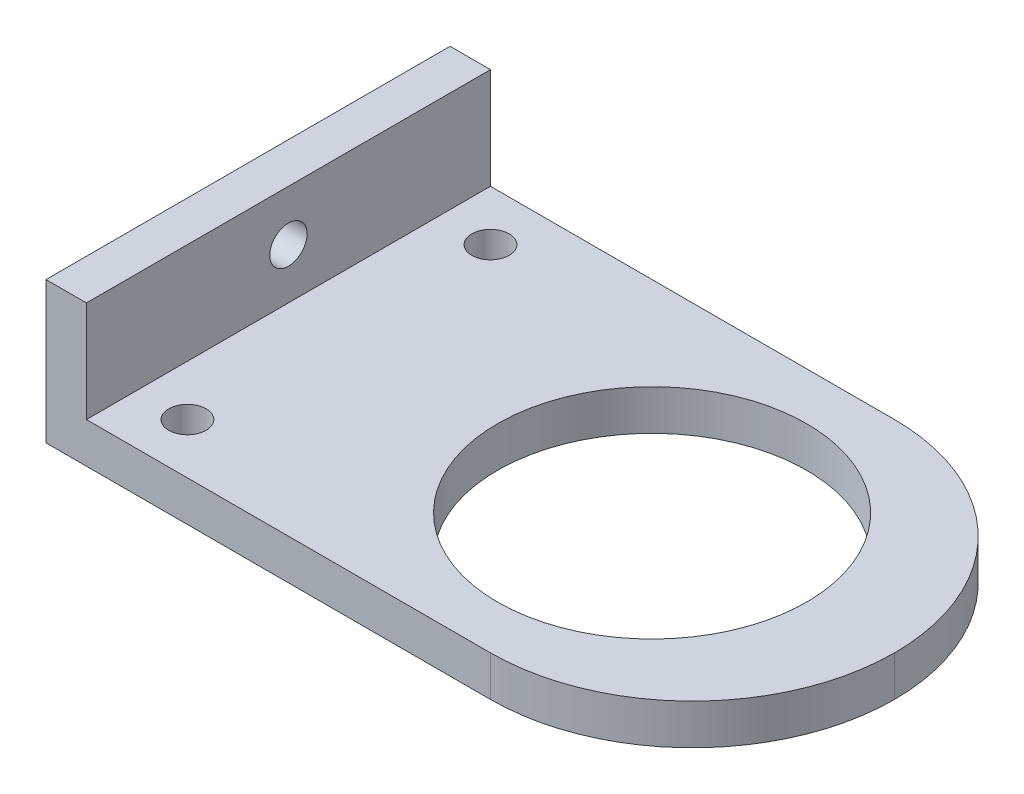
SolidWorks part; units mm, degrees
ref_plane "正面" through (0, 0, 0) normal (0, 0, 1) x (1, 0, 0)
ref_plane "平面" through (0, 0, 0) normal (0, 1, 0) x (1, 0, 0)
ref_plane "右側面" through (0, 0, 0) normal (1, 0, 0) x (0, 0, -1)
sketch "ｽｹｯﾁ1" plane through (0, 0, 0) normal (0, 0, 1) x (1, 0, 0)
  line L0 (0, 10) -> (0, 0)
  line L1 (0, 0) -> (60, 0)
  line L2 (-4, 10) -> (-4, -4)
  line L3 (-4, -4) -> (60, -4)
  line L4 (0, 10) -> (-4, 10)
  line L5 (60, 0) -> (60, -4)
  dimension "D1" = 10
  dimension "D2" = 60
  dimension "D3" = 4
extrude "ﾎﾞｽ - 押し出し1" add sketch "ｽｹｯﾁ1" along normal blind 40
sketch "ｽｹｯﾁ2" plane through (0, 0, 0) normal (1, 0, 0) x (0, 0, -1)
  line L1 (-40, 10) -> (0, 10) construction
  line L2 (-40, 0) -> (-40, 10) construction
  circle A1 centre (-20, 5) radius 1.85
  dimension "D4" = 20
  dimension "D5" = 5
  dimension "D6" = 3.7
extrude "ｶｯﾄ - 押し出し1" cut sketch "ｽｹｯﾁ2" against normal blind 40
sketch "ｽｹｯﾁ4" plane through (0, 0, 0) normal (0, 1, 0) x (1, 0, 0)
  line L0 (-4, -40) -> (-4, 0) construction
  line L1 (60, 0) -> (0, 0) construction
  line L2 (0, -40) -> (0, 0) construction
  line L3 (60, -40) -> (0, -40) construction
  circle A0 centre (36, -20) radius 15.3
  circle A1 centre (5, -5) radius 1.85
  circle A2 centre (5, -35) radius 1.85
  dimension "D1" = 30.6
  dimension "D2" = 40
  dimension "D3" = 20
  dimension "D4" = 5
  dimension "D5" = 5
  dimension "D6" = 3.7
  dimension "D7" = 5
  dimension "D8" = 3.7
extrude "ｶｯﾄ - 押し出し2" cut sketch "ｽｹｯﾁ4" against normal blind 40
fillet "ﾌｨﾚｯﾄ1" radius 20 2 edges at (60, -2, 0) (60, -2, 40)
